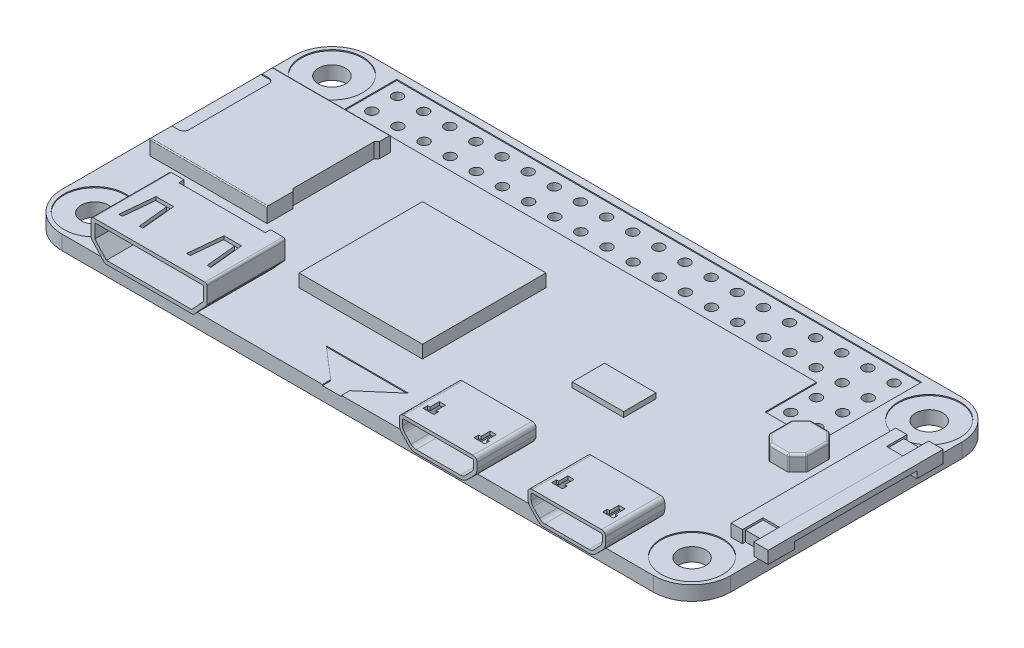
SolidWorks part; units mm, degrees
ref_plane "Front Plane" through (0, 0, 0) normal (0, 0, 1) x (1, 0, 0)
ref_plane "Top Plane" through (0, 0, 0) normal (0, 1, 0) x (1, 0, 0)
ref_plane "Right Plane" through (0, 0, 0) normal (1, 0, 0) x (0, 0, -1)
sketch "Sketch1" plane through (0, 0, 0) normal (0, 1, 0) x (1, 0, 0)
  line L1 (-28.75, 15) -> (28.75, 15)
  line L2 (-32.5, 11.25) -> (-32.5, -11.25)
  line L3 (-28.75, -15) -> (28.75, -15)
  line L4 (32.5, 11.25) -> (32.5, -11.25)
  line L5 (-32.5, 15) -> (32.5, -15) construction
  line L6 (-32.5, -15) -> (32.5, 15) construction
  arc A0 (-32.5, -11.25) -> (-28.75, -15) centre (-28.75, -11.25) ccw
  arc A1 (28.75, -15) -> (32.5, -11.25) centre (28.75, -11.25) ccw
  arc A2 (28.75, 15) -> (32.5, 11.25) centre (28.75, 11.25) cw
  arc A3 (-28.75, 15) -> (-32.5, 11.25) centre (-28.75, 11.25) ccw
  point P0 (0, 0)
  dimension "D3" = 3.75
  dimension "D1" = 65
  dimension "D2" = 30
extrude "Boss-Extrude1" add sketch "Sketch1" along normal blind 1.4 contours L1 A2 L4 A1 L3 A0 L2 A3
sketch "Sketch2" plane through (0, 1.4, 0) normal (0, 1, 0) x (1, 0, 0)
  line L0 (0, 15) -> (0, -15) construction
  line L1 (-28.75, 15) -> (28.75, 15) construction
  line L2 (-28.75, -15) -> (28.75, -15) construction
  line L3 (-32.5, 0) -> (32.5, 0) construction
  line L4 (-32.5, 11.25) -> (-32.5, -11.25) construction
  line L5 (32.5, 11.25) -> (32.5, -11.25) construction
  circle A0 centre (-29.025, 11.525) radius 1.325
  circle A2 centre (29.025, 11.525) radius 1.325
  circle A3 centre (29.025, -11.525) radius 1.325
  circle A4 centre (-29.025, -11.525) radius 1.325
  dimension "D1" = 2.65
  dimension "D2" = 2.15
  dimension "D3" = 2.15
extrude "Cut-Extrude1" cut sketch "Sketch2" against normal through all
sketch "Sketch3" plane through (0, 1.4, 0) normal (0, 1, 0) x (1, 0, 0)
  line L0 (-24.128, 13) -> (-24.128, 10.5) construction
  line L3 (-28.75, 15) -> (28.75, 15) construction
  line L5 (-32.5, 11.25) -> (-32.5, -11.25) construction
  circle A0 centre (-24.128, 13) radius 0.5
  circle A1 centre (-24.128, 10.5) radius 0.5
  dimension "D1" = 1
  dimension "D3" = 1.5
  dimension "D4" = 7.872
  dimension "D2" = 2.5
extrude "Cut-Extrude2" cut sketch "Sketch3" against normal through all
pattern_linear "LPattern1" count 20 spacing 2.54 along (1, 0, 0) of "Cut-Extrude2"
sketch "Sketch5" plane through (0, 1.4, 0) normal (0, 1, 0) x (1, 0, 0)
  line L0 (21.592, 10.5) -> (21.592, 5.5) construction
  line L1 (24.132, 10.5) -> (24.132, 5.5) construction
  line L2 (24.132, 5.5) -> (21.592, 5.5) construction
  circle A0 centre (21.592, 5.5) radius 0.5
  circle A1 centre (24.132, 5.5) radius 0.5
  circle A2 centre (21.592, 8) radius 0.5
  circle A3 centre (24.132, 8) radius 0.5
  dimension "D1" = 2.5
  dimension "D2" = 1
extrude "Cut-Extrude4" cut sketch "Sketch5" against normal through all
sketch "Sketch4" plane through (0, 1.4, 0) normal (0, 1, 0) x (1, 0, 0)
  line L0 (0, 0) -> (0, 14.3) construction
  line L1 (-24.128, 13) -> (-24.128, 10.5) construction
  line L2 (-25.5, 14.3) -> (25.5, 14.3)
  line L3 (-25.5, 14.3) -> (-25.5, 9.2)
  line L4 (-25.5, 9.2) -> (20.4, 9.2)
  line L5 (25.5, 14.3) -> (25.5, 9.2)
  line L6 (-25.5, 11.75) -> (-24.128, 11.75) construction
  line L7 (20.4, 9.2) -> (25.5, 9.2) construction
  line L8 (-2.5, -15) -> (-2.5, -11.55) construction
  line L9 (25.5, 9.2) -> (25.5, 4.2)
  line L10 (25.5, 4.2) -> (20.4, 4.2)
  line L11 (20.4, 9.2) -> (20.4, 4.2)
  line L12 (-28.75, -15) -> (28.75, -15) construction
  line L13 (-6.5, -11.55) -> (1.5, -11.55)
  line L14 (1.5, -11.55) -> (-1.575, -14.2)
  line L15 (-1.575, -14.2) -> (-1.575, -15)
  line L16 (-1.575, -15) -> (-3.425, -15)
  line L17 (-3.425, -15) -> (-3.425, -14.2)
  line L18 (-3.425, -14.2) -> (-6.5, -11.55)
  line L19 (-32.5, 11.25) -> (-32.5, -11.25) construction
  circle A0 centre (-29.025, 11.525) radius 3
  circle A1 centre (-29.025, -11.525) radius 3
  circle A2 centre (29.025, -11.525) radius 3
  circle A3 centre (29.025, 11.525) radius 3
  point P23 (-24.128, 11.75)
  point P26 (-25.5, 11.75)
  dimension "D1" = 6
  dimension "D2" = 5.1
  dimension "D3" = 51
  dimension "D4" = 5.1
  dimension "D5" = 5
  dimension "D6" = 8
  dimension "D7" = 1.85
  dimension "D8" = 3.45
  dimension "D9" = 0.8
  dimension "D10" = 30
extrude "Cut-Extrude3" cut sketch "Sketch4" against normal blind 0.1
sketch "Sketch6" plane through (0, 1.4, 0) normal (0, 1, 0) x (1, 0, 0)
  line L0 (-28.75, -15) -> (-3.425, -15) construction
  line L1 (-12.7, 4) -> (-0.7, 4)
  line L2 (-12.7, 4) -> (-12.7, -8)
  line L3 (-12.7, -8) -> (-0.7, -8)
  line L4 (-0.7, 4) -> (-0.7, -8)
  line L5 (-12.7, 4) -> (-0.7, -8) construction
  line L6 (-12.7, -8) -> (-0.7, 4) construction
  line L7 (-32.5, 11.25) -> (-32.5, -11.25) construction
  point P0 (-6.7, -2)
  dimension "D1" = 12
  dimension "D2" = 7
  dimension "D3" = 19.8
extrude "Boss-Extrude2" add sketch "Sketch6" along normal blind 1.25
sketch "Sketch7" plane through (0, 1.4, 0) normal (0, 1, 0) x (1, 0, 0)
  line L0 (-19.65, 7.85) -> (-19.65, 6.75)
  line L1 (-31.05, 7.85) -> (-19.65, 7.85)
  line L2 (-31.05, 7.85) -> (-31.05, -4.15) construction
  line L3 (-31.05, -4.15) -> (-19.65, -4.15)
  line L4 (-19.65, 7.85) -> (-19.65, -4.15) construction
  line L5 (-19.65, 6.75) -> (-19.9, 6.5)
  line L6 (-19.9, 6.5) -> (-19.9, -1.4)
  line L7 (-19.9, -1.4) -> (-19.65, -1.65)
  line L8 (-19.65, -1.65) -> (-19.65, -4.15)
  line L9 (-31.05, 7.85) -> (-31.05, 6.75)
  line L10 (-31.05, 6.75) -> (-30.4, 6.75)
  line L11 (-29.9, 6.25) -> (-29.9, -1.5)
  line L12 (-30.4, -2) -> (-31.05, -2)
  line L13 (-31.05, -2) -> (-31.05, -4.15)
  line L14 (-28.75, 15) -> (28.75, 15) construction
  line L15 (-32.5, 11.25) -> (-32.5, -11.25) construction
  arc A0 (-29.9, -1.5) -> (-30.4, -2) centre (-30.4, -1.5) cw
  arc A1 (-30.4, 6.75) -> (-29.9, 6.25) centre (-30.4, 6.25) cw
  dimension "D9" = 0.5
  dimension "D1" = 11.4
  dimension "D2" = 12
  dimension "D3" = 2.5
  dimension "D4" = 1.1
  dimension "D5" = 0.25
  dimension "D6" = 1.1
  dimension "D7" = 2.15
  dimension "D8" = 1.15
  dimension "D10" = 7.15
  dimension "D11" = 1.45
extrude "Boss-Extrude3" add sketch "Sketch7" along normal blind 1.45
fillet "Fillet2" radius 0.1 2 edges at (-25.35, 2.85, -7.85) (-25.35, 2.85, 4.15)
sketch "Sketch8" plane through (-29.9, 0, 0) normal (-1, 0, 0) x (0, 0, 1)
  line L0 (-7.85, 2.75) -> (-7.85, 1.4) construction
  line L1 (-7.75, 2.75) -> (4.05, 2.75)
  line L2 (-7.75, 2.75) -> (-7.75, 1.5)
  line L3 (-7.75, 1.5) -> (4.05, 1.5)
  line L4 (4.05, 2.75) -> (4.05, 1.5)
  line L5 (-6.25, 2.85) -> (1.5, 2.85) construction
  line L6 (4.15, 2.75) -> (4.15, 1.4) construction
  line L7 (-6.25, 1.4) -> (1.5, 1.4) construction
  dimension "D1" = 0.1
  dimension "D2" = 0.1
  dimension "D3" = 0.1
  dimension "D4" = 0.1
extrude "Cut-Extrude5" cut sketch "Sketch8" against normal blind 9.5 and the other way through all
sketch "Sketch9" plane through (0, 0, 15) normal (0, 0, 1) x (1, 0, 0)
  line L0 (-19.875, 1.4) -> (-19.875, 4.7) construction
  line L1 (-28.75, 1.4) -> (-3.425, 1.4) construction
  line L2 (-25.5, 4.7) -> (-14.25, 4.7)
  line L3 (-14.25, 4.7) -> (-14.25, 2.85)
  line L4 (-14.25, 2.85) -> (-15.575, 1.4)
  line L5 (-12.7, 1.4) -> (-0.7, 1.4) construction
  line L6 (-15.575, 1.4) -> (-24.175, 1.4)
  line L7 (-24.175, 1.4) -> (-25.5, 2.85)
  line L8 (-25.5, 2.85) -> (-25.5, 4.7)
  line L9 (-32.5, 1.4) -> (-32.5, 0) construction
  dimension "D1" = 3.3
  dimension "D2" = 1.85
  dimension "D3" = 8.6
  dimension "D4" = 11.25
  dimension "D5" = 7
extrude "Boss-Extrude4" add sketch "Sketch9" along normal blind 0.4 and the other way blind 7.2 separate body
fillet "Fillet1" radius 0.2 6 edges at (-15.575, 1.4, 11.6) (-24.175, 1.4, 11.6) (-25.5, 2.85, 11.6) (-14.25, 2.85, 11.6) (-25.5, 4.7, 11.6) (-14.25, 4.7, 11.6)
sketch "Sketch10" plane through (0, 0, 15.4) normal (0, 0, 1) x (1, 0, 0)
  line L12 (-25.15, 4.35) -> (-25.15, 2.9858)
  line L13 (-25.15, 2.9858) -> (-24.0207, 1.75)
  line L14 (-24.0207, 1.75) -> (-15.7293, 1.75)
  line L15 (-15.7293, 1.75) -> (-14.6, 2.9858)
  line L16 (-14.6, 2.9858) -> (-14.6, 4.35)
  line L17 (-14.6, 4.35) -> (-25.15, 4.35)
  line L18 (-25.15, 4.35) -> (-25.15, 2.9858)
  line L19 (-25.15, 2.9858) -> (-24.0207, 1.75)
  line L20 (-24.0207, 1.75) -> (-15.7293, 1.75)
  line L21 (-15.7293, 1.75) -> (-14.6, 2.9858)
  line L22 (-14.6, 2.9858) -> (-14.6, 4.35)
  line L23 (-14.6, 4.35) -> (-25.15, 4.35)
  dimension "D1" = 0.35
extrude "Cut-Extrude6" cut sketch "Sketch10" against normal blind 7
sketch "Sketch11" plane through (0, 0, 8.4) normal (0, 0, 1) x (1, 0, 0)
  line L0 (-19.875, 3.5) -> (-19.875, 1.75) construction
  line L1 (-23.375, 2.95) -> (-16.375, 2.95)
  line L2 (-23.375, 2.95) -> (-23.375, 3.5)
  line L3 (-23.375, 3.5) -> (-16.375, 3.5)
  line L4 (-16.375, 2.95) -> (-16.375, 3.5)
  line L5 (-24.0207, 1.75) -> (-15.7293, 1.75) construction
  line L6 (-24.0207, 1.75) -> (-15.7293, 1.75) construction
  dimension "D1" = 7
  dimension "D2" = 0.55
  dimension "D3" = 1.2
extrude "Boss-Extrude5" add sketch "Sketch11" along normal blind 3.5
sketch "Sketch12" plane through (0, 4.35, 0) normal (0, -1, 0) x (1, 0, 0)
  line L0 (-19.875, 7.8) -> (-19.875, 15.4) construction
  line L1 (-14.45, 7.8) -> (-25.3, 7.8) construction
  line L2 (-14.45, 15.4) -> (-25.3, 15.4) construction
  line L3 (-23.175, 10.57) -> (-23.175, 13.4458) construction
  line L4 (-24.025, 10.57) -> (-22.325, 10.57)
  line L5 (-22.325, 10.57) -> (-22, 13.87)
  line L6 (-22, 13.87) -> (-22.3517, 13.87)
  line L7 (-22.3517, 13.87) -> (-22.6422, 10.92)
  line L8 (-22.6422, 10.92) -> (-23.7078, 10.92)
  line L9 (-23.9983, 13.87) -> (-23.7078, 10.92)
  line L10 (-24.35, 13.87) -> (-23.9983, 13.87)
  line L11 (-24.025, 10.57) -> (-24.35, 13.87)
  line L12 (-16.575, 10.57) -> (-16.575, 13.4458) construction
  line L13 (-15.725, 10.57) -> (-15.4, 13.87)
  line L14 (-15.4, 13.87) -> (-15.7517, 13.87)
  line L15 (-15.7517, 13.87) -> (-16.0422, 10.92)
  line L16 (-17.1078, 10.92) -> (-16.0422, 10.92)
  line L17 (-17.3983, 13.87) -> (-17.1078, 10.92)
  line L18 (-17.75, 13.87) -> (-17.3983, 13.87)
  line L19 (-17.425, 10.57) -> (-17.75, 13.87)
  line L20 (-15.725, 10.57) -> (-17.425, 10.57)
  point P15 (-23.175, 10.92)
  point P28 (-16.575, 10.92)
  dimension "D1" = 0.35
  dimension "D2" = 0.35
  dimension "D3" = 3.3
  dimension "D4" = 2.35
  dimension "D5" = 1.7
  dimension "D6" = 2.77
  dimension "D7" = 4.25
extrude "Cut-Extrude7" cut sketch "Sketch12" against normal through all
sketch "Sketch13" plane through (0, 0, 7.8) normal (0, 0, -1) x (-1, 0, 0)
  line L0 (14.45, 4.7) -> (25.3, 4.7) construction
  line L1 (15.675, 4.7) -> (24.075, 4.7)
  line L2 (15.675, 4.7) -> (15.675, 3.3)
  line L3 (15.675, 3.3) -> (24.075, 3.3)
  line L4 (24.075, 4.7) -> (24.075, 3.3)
  line L5 (19.875, 1.4) -> (19.875, 4.7) construction
  line L6 (24.0868, 1.4) -> (15.6632, 1.4) construction
  dimension "D1" = 8.4
  dimension "D2" = 1.4
extrude "Cut-Extrude8" cut sketch "Sketch13" against normal blind 0.5
sketch "Sketch15" plane through (0, 0, 15) normal (0, 0, 1) x (1, 0, 0)
  line L0 (21.575, 1.4) -> (21.575, 4) construction
  line L1 (-1.575, 1.4) -> (28.75, 1.4) construction
  line L2 (18.2, 4) -> (24.95, 4)
  line L3 (25.35, 3.6) -> (25.35, 3.0523)
  line L4 (25.0714, 2.3598) -> (24.4452, 1.7075)
  line L5 (23.7238, 1.4) -> (19.4262, 1.4)
  line L6 (32.5, 1.4) -> (32.5, 0) construction
  line L7 (18.0786, 2.3598) -> (18.7048, 1.7075)
  line L8 (17.8, 3.6) -> (17.8, 3.0523)
  line L9 (15.325, 0) -> (15.325, 5.5788) construction
  line L10 (-28.75, 0) -> (28.75, 0) construction
  line L11 (9.075, 1.4) -> (9.075, 4) construction
  line L12 (12.85, 3.6) -> (12.85, 3.0523)
  line L13 (12.5714, 2.3598) -> (11.9452, 1.7075)
  line L14 (6.9262, 1.4) -> (11.2238, 1.4)
  line L15 (5.5786, 2.3598) -> (6.2048, 1.7075)
  line L16 (5.3, 3.6) -> (5.3, 3.0523)
  line L17 (12.45, 4) -> (5.7, 4)
  arc A0 (24.4452, 1.7075) -> (23.7238, 1.4) centre (23.7238, 2.4) cw
  arc A1 (18.7048, 1.7075) -> (19.4262, 1.4) centre (19.4262, 2.4) ccw
  arc A2 (25.35, 3.0523) -> (25.0714, 2.3598) centre (24.35, 3.0523) cw
  arc A3 (18.0786, 2.3598) -> (17.8, 3.0523) centre (18.8, 3.0523) cw
  arc A4 (24.95, 4) -> (25.35, 3.6) centre (24.95, 3.6) cw
  arc A5 (17.8, 3.6) -> (18.2, 4) centre (18.2, 3.6) cw
  arc A6 (12.85, 3.6) -> (12.45, 4) centre (12.45, 3.6) ccw
  arc A7 (5.7, 4) -> (5.3, 3.6) centre (5.7, 3.6) ccw
  arc A8 (12.5714, 2.3598) -> (12.85, 3.0523) centre (11.85, 3.0523) ccw
  arc A9 (5.3, 3.0523) -> (5.5786, 2.3598) centre (6.3, 3.0523) ccw
  arc A10 (11.9452, 1.7075) -> (11.2238, 1.4) centre (11.2238, 2.4) cw
  arc A11 (6.2048, 1.7075) -> (6.9262, 1.4) centre (6.9262, 2.4) ccw
  point P14 (24.15, 1.4)
  point P17 (19, 1.4)
  point P20 (25.35, 2.65)
  point P23 (17.8, 2.65)
  point P26 (25.35, 4)
  point P29 (17.8, 4)
  point P54 (12.85, 4)
  point P55 (5.3, 4)
  point P56 (12.85, 2.65)
  point P57 (5.3, 2.65)
  point P58 (11.65, 1.4)
  point P59 (6.5, 1.4)
  dimension "D6" = 1
  dimension "D7" = 0.4
  dimension "D1" = 7.55
  dimension "D2" = 2.6
  dimension "D3" = 1.35
  dimension "D4" = 5.15
  dimension "D5" = 7.15
  dimension "D8" = 4.95
extrude "Boss-Extrude6" add sketch "Sketch15" along normal blind 1.25 and the other way blind 4.5
sketch "Sketch16" plane through (0, 0, 16.25) normal (0, 0, 1) x (1, 0, 0)
  line L12 (12.45, 3.68) -> (5.7, 3.68)
  line L13 (5.62, 3.6) -> (5.62, 3.0523)
  line L14 (5.8095, 2.5814) -> (6.4357, 1.9291)
  line L15 (6.9262, 1.72) -> (11.2238, 1.72)
  line L16 (11.7143, 1.9291) -> (12.3405, 2.5814)
  line L17 (12.53, 3.0523) -> (12.53, 3.6)
  line L18 (12.45, 3.68) -> (5.7, 3.68)
  line L19 (5.62, 3.6) -> (5.62, 3.0523)
  line L20 (5.8095, 2.5814) -> (6.4357, 1.9291)
  line L21 (6.9262, 1.72) -> (11.2238, 1.72)
  line L22 (11.7143, 1.9291) -> (12.3405, 2.5814)
  line L23 (12.53, 3.0523) -> (12.53, 3.6)
  line L30 (24.2143, 1.9291) -> (24.8405, 2.5814)
  line L31 (25.03, 3.0523) -> (25.03, 3.6)
  line L32 (24.95, 3.68) -> (18.2, 3.68)
  line L33 (18.12, 3.6) -> (18.12, 3.0523)
  line L34 (18.3095, 2.5814) -> (18.9357, 1.9291)
  line L35 (19.4262, 1.72) -> (23.7238, 1.72)
  line L36 (24.2143, 1.9291) -> (24.8405, 2.5814)
  line L37 (25.03, 3.0523) -> (25.03, 3.6)
  line L38 (24.95, 3.68) -> (18.2, 3.68)
  line L39 (18.12, 3.6) -> (18.12, 3.0523)
  line L40 (18.3095, 2.5814) -> (18.9357, 1.9291)
  line L41 (19.4262, 1.72) -> (23.7238, 1.72)
  arc A12 (12.53, 3.6) -> (12.45, 3.68) centre (12.45, 3.6) ccw
  arc A13 (5.7, 3.68) -> (5.62, 3.6) centre (5.7, 3.6) ccw
  arc A14 (5.62, 3.0523) -> (5.8095, 2.5814) centre (6.3, 3.0523) ccw
  arc A15 (6.4357, 1.9291) -> (6.9262, 1.72) centre (6.9262, 2.4) ccw
  arc A16 (11.2238, 1.72) -> (11.7143, 1.9291) centre (11.2238, 2.4) ccw
  arc A17 (12.3405, 2.5814) -> (12.53, 3.0523) centre (11.85, 3.0523) ccw
  arc A18 (12.53, 3.6) -> (12.45, 3.68) centre (12.45, 3.6) ccw
  arc A19 (5.7, 3.68) -> (5.62, 3.6) centre (5.7, 3.6) ccw
  arc A20 (5.62, 3.0523) -> (5.8095, 2.5814) centre (6.3, 3.0523) ccw
  arc A21 (6.4357, 1.9291) -> (6.9262, 1.72) centre (6.9262, 2.4) ccw
  arc A22 (11.2238, 1.72) -> (11.7143, 1.9291) centre (11.2238, 2.4) ccw
  arc A23 (12.3405, 2.5814) -> (12.53, 3.0523) centre (11.85, 3.0523) ccw
  arc A30 (23.7238, 1.72) -> (24.2143, 1.9291) centre (23.7238, 2.4) ccw
  arc A31 (24.8405, 2.5814) -> (25.03, 3.0523) centre (24.35, 3.0523) ccw
  arc A32 (25.03, 3.6) -> (24.95, 3.68) centre (24.95, 3.6) ccw
  arc A33 (18.2, 3.68) -> (18.12, 3.6) centre (18.2, 3.6) ccw
  arc A34 (18.12, 3.0523) -> (18.3095, 2.5814) centre (18.8, 3.0523) ccw
  arc A35 (18.9357, 1.9291) -> (19.4262, 1.72) centre (19.4262, 2.4) ccw
  arc A36 (23.7238, 1.72) -> (24.2143, 1.9291) centre (23.7238, 2.4) ccw
  arc A37 (24.8405, 2.5814) -> (25.03, 3.0523) centre (24.35, 3.0523) ccw
  arc A38 (25.03, 3.6) -> (24.95, 3.68) centre (24.95, 3.6) ccw
  arc A39 (18.2, 3.68) -> (18.12, 3.6) centre (18.2, 3.6) ccw
  arc A40 (18.12, 3.0523) -> (18.3095, 2.5814) centre (18.8, 3.0523) ccw
  arc A41 (18.9357, 1.9291) -> (19.4262, 1.72) centre (19.4262, 2.4) ccw
  dimension "D1" = 0.32
  dimension "D2" = 0.32
extrude "Cut-Extrude9" cut sketch "Sketch16" against normal blind 5.25
sketch "Sketch17" plane through (0, 0, 11) normal (0, 0, 1) x (1, 0, 0)
  line L0 (12.85, 3.3262) -> (17.8, 3.3262) construction
  line L1 (12.85, 3.0523) -> (12.85, 3.6) construction
  line L2 (17.8, 3.6) -> (17.8, 3.0523) construction
  line L3 (15.325, 3.3262) -> (15.325, 1.4) construction
  line L4 (11.2238, 1.4) -> (19.4262, 1.4) construction
  line L5 (9.075, 1.72) -> (9.075, 3.68) construction
  line L6 (6.9262, 1.72) -> (11.2238, 1.72) construction
  line L7 (12.45, 3.68) -> (5.7, 3.68) construction
  line L8 (6.9262, 1.72) -> (11.2238, 1.72) construction
  line L9 (7.5, 3.32) -> (10.65, 3.32)
  line L10 (7.5, 3.32) -> (7.5, 2.92)
  line L11 (7.5, 2.92) -> (10.65, 2.92)
  line L12 (10.65, 3.32) -> (10.65, 2.92)
  line L13 (7.5, 3.32) -> (10.65, 2.92) construction
  line L14 (7.5, 2.92) -> (10.65, 3.32) construction
  line L15 (23.15, 2.92) -> (20, 3.32) construction
  line L16 (23.15, 3.32) -> (20, 2.92) construction
  line L17 (20, 3.32) -> (20, 2.92)
  line L18 (23.15, 2.92) -> (20, 2.92)
  line L19 (23.15, 3.32) -> (23.15, 2.92)
  line L20 (23.15, 3.32) -> (20, 3.32)
  point P16 (9.075, 3.12)
  point P27 (21.575, 3.12)
  dimension "D1" = 3.15
  dimension "D2" = 0.4
  dimension "D3" = 1.4
extrude "Boss-Extrude7" add sketch "Sketch17" along normal blind 3.5
sketch "Sketch18" plane through (0, 4, 0) normal (0, 1, 0) x (1, 0, 0)
  line L0 (9.075, -16.25) -> (9.075, -10.5) construction
  line L1 (12.45, -16.25) -> (5.7, -16.25) construction
  line L2 (6.9262, -10.5) -> (11.2238, -10.5) construction
  line L3 (12.85, -16.25) -> (17.8, -16.25) construction
  line L4 (15.325, -16.25) -> (15.325, -10.5) construction
  line L5 (6.6, -13.37) -> (6.6, -14.72) construction
  line L6 (6.9, -13.37) -> (6.3, -13.37)
  line L7 (6.3, -13.37) -> (6.3, -14.27)
  line L8 (6.3, -14.27) -> (6.075, -14.27)
  line L9 (6.075, -14.27) -> (6.075, -14.72)
  line L10 (6.075, -14.72) -> (7.125, -14.72)
  line L11 (7.125, -14.27) -> (7.125, -14.72)
  line L12 (6.9, -14.27) -> (7.125, -14.27)
  line L13 (6.9, -13.37) -> (6.9, -14.27)
  line L14 (11.55, -13.37) -> (11.55, -14.72) construction
  line L15 (11.25, -13.37) -> (11.25, -14.27)
  line L16 (11.25, -14.27) -> (11.025, -14.27)
  line L17 (11.025, -14.27) -> (11.025, -14.72)
  line L18 (12.075, -14.72) -> (11.025, -14.72)
  line L19 (12.075, -14.27) -> (12.075, -14.72)
  line L20 (11.85, -14.27) -> (12.075, -14.27)
  line L21 (11.85, -13.37) -> (11.85, -14.27)
  line L22 (11.25, -13.37) -> (11.85, -13.37)
  line L23 (19.1, -13.37) -> (19.1, -14.72) construction
  line L24 (24.05, -13.37) -> (24.05, -14.72) construction
  line L25 (21.575, -16.25) -> (21.575, -10.5) construction
  line L26 (19.4, -13.37) -> (18.8, -13.37)
  line L27 (18.8, -13.37) -> (18.8, -14.27)
  line L28 (18.8, -14.27) -> (18.575, -14.27)
  line L29 (18.575, -14.27) -> (18.575, -14.72)
  line L30 (18.575, -14.72) -> (19.625, -14.72)
  line L31 (19.625, -14.27) -> (19.625, -14.72)
  line L32 (19.4, -14.27) -> (19.625, -14.27)
  line L33 (19.4, -13.37) -> (19.4, -14.27)
  line L34 (23.75, -13.37) -> (23.75, -14.27)
  line L35 (23.75, -14.27) -> (23.525, -14.27)
  line L36 (23.525, -14.27) -> (23.525, -14.72)
  line L37 (24.575, -14.72) -> (23.525, -14.72)
  line L38 (24.575, -14.27) -> (24.575, -14.72)
  line L39 (24.35, -14.27) -> (24.575, -14.27)
  line L40 (24.35, -13.37) -> (24.35, -14.27)
  line L41 (23.75, -13.37) -> (24.35, -13.37)
  dimension "D1" = 1.05
  dimension "D2" = 1.35
  dimension "D3" = 0.9
  dimension "D4" = 0.6
  dimension "D5" = 3.9
  dimension "D6" = 1.53
extrude "Cut-Extrude10" cut sketch "Sketch18" against normal up to surface (0.32 mm away) up to face at (9.075, 3.68, 13.625)
sketch "Sketch19" plane through (32.5, 0, 0) normal (1, 0, 0) x (0, 0, -1)
  line L0 (0, 1.4) -> (0, 2.6) construction
  line L1 (11.25, 1.4) -> (-11.25, 1.4) construction
  line L2 (-8.5, 2.6) -> (8.5, 2.6)
  line L3 (8.5, 2.6) -> (8.5, 1.4)
  line L4 (6.5, 1.4) -> (6.75, 1.4) construction
  line L5 (8.5, 1.4) -> (5.95, 1.4)
  line L6 (-1.4, 1.4) -> (6.5, 1.4) construction
  line L7 (5.95, 1.4) -> (5.95, 2.05)
  line L8 (5.95, 2.05) -> (-5.95, 2.05)
  line L9 (-5.95, 2.05) -> (-5.95, 1.4)
  line L10 (-5.95, 1.4) -> (-8.5, 1.4)
  line L11 (-8, 1.4) -> (4, 1.4) construction
  line L12 (-8.5, 1.4) -> (-8.5, 2.6)
  line L13 (15, 1.4) -> (15, 0) construction
  dimension "D1" = 1.2
  dimension "D2" = 0.55
  dimension "D3" = 11.9
  dimension "D4" = 17
  dimension "D5" = 6.5
extrude "Boss-Extrude8" add sketch "Sketch19" along normal blind 0.9 and the other way blind 0.5
sketch "Sketch20" plane through (0, 1.4, 0) normal (0, 1, 0) x (1, 0, 0)
  line L0 (33.4, 0) -> (29.3, 0) construction
  line L1 (33.4, 8.5) -> (33.4, -8.5) construction
  line L2 (32, 6) -> (30.4, 6)
  line L3 (32, 8.5) -> (32, -8.5) construction
  line L4 (30.4, 6) -> (30.4, 8)
  line L5 (30.4, 8) -> (29.3, 8)
  line L6 (29.3, 8) -> (29.3, -8)
  line L7 (29.3, -8) -> (30.4, -8)
  line L8 (30.4, -8) -> (30.4, -6)
  line L9 (30.4, -6) -> (32, -6)
  line L10 (32, -6) -> (32, 6)
  dimension "D1" = 16
  dimension "D2" = 2.7
  dimension "D3" = 1.1
  dimension "D4" = 12
extrude "Boss-Extrude9" add sketch "Sketch20" along normal blind 1.19
sketch "Sketch21" plane through (0, 1.4, 0) normal (0, 1, 0) x (1, 0, 0)
  line L0 (32, 6) -> (32, 8.5) construction
  line L1 (30.4, 6) -> (32, 6)
  line L2 (30.4, 6) -> (30.4, 7.7)
  line L3 (30.4, 7.7) -> (32, 7.7)
  line L4 (32, 6) -> (32, 7.7)
  line L5 (32, 8.5) -> (32, -8.5) construction
  line L6 (30.4, -6) -> (32, -6)
  line L7 (30.4, -6) -> (30.4, -7.7)
  line L8 (30.4, -7.7) -> (32, -7.7)
  line L9 (32, -6) -> (32, -7.7)
  dimension "D1" = 1.7
extrude "Boss-Extrude10" add sketch "Sketch21" along normal blind 1
sketch "Sketch22" plane through (0, 1.4, 0) normal (0, 1, 0) x (1, 0, 0)
  line L0 (32.5, -8.5) -> (32.5, -11.25) construction
  line L1 (23.85, 4.25) -> (27.5, 4.25)
  line L2 (23.85, 4.25) -> (23.85, 0.25)
  line L3 (23.85, 0.25) -> (27.5, 0.25)
  line L4 (27.5, 4.25) -> (27.5, 0.25)
  line L5 (-28.75, 15) -> (28.75, 15) construction
  dimension "D1" = 3.65
  dimension "D2" = 4
  dimension "D3" = 5
  dimension "D4" = 10.75
extrude "Boss-Extrude11" add sketch "Sketch22" along normal blind 1.5
chamfer "Chamfer1" distance 0.9 angle 45 4 edges at (23.85, 2.15, -4.25) (27.5, 2.15, -4.25) (27.5, 2.15, -0.25) (23.85, 2.15, -0.25)
sketch "Sketch23" plane through (0, 1.4, 0) normal (0, 1, 0) x (1, 0, 0)
  line L0 (-28.75, 15) -> (28.75, 15) construction
  line L1 (9, 0) -> (14, 0)
  line L2 (9, 0) -> (9, -3.15)
  line L3 (9, -3.15) -> (14, -3.15)
  line L4 (14, 0) -> (14, -3.15)
  line L5 (32.5, -8.5) -> (32.5, -11.25) construction
  dimension "D1" = 5
  dimension "D2" = 3.15
  dimension "D3" = 15
  dimension "D4" = 18.5
extrude "Boss-Extrude12" add sketch "Sketch23" along normal blind 0.5
fillet "Fillet3" radius 0.2 16 edges at (27.05, 2.9, -3.8) (27.5, 2.9, -2.25) (27.05, 2.9, -0.7) (25.675, 2.9, -0.25) (24.3, 2.9, -0.7) (23.85, 2.9, -2.25) (24.3, 2.9, -3.8) (25.675, 2.9, -4.25) (26.6, 2.15, -4.25) (24.75, 2.15, -4.25) (23.85, 2.15, -3.35) (24.75, 2.15, -0.25) (23.85, 2.15, -1.15) (27.5, 2.15, -3.35) (27.5, 2.15, -1.15) (26.6, 2.15, -0.25)
sketch "草图1" plane through (0, 0, 0) normal (0, -1, 0) x (1, 0, 0)
  circle A0 centre (22.059, 8.8833) radius 0.75
  circle A1 centre (22.059, 11.1732) radius 0.75
  circle A2 centre (8.3246, 12.8981) radius 0.6
  circle A3 centre (10.1975, 12.8981) radius 0.6
  dimension "D1" = 1.5
  dimension "D2" = 1.2
extrude "凸台-拉伸1" add sketch "草图1" along normal blind 0.1
